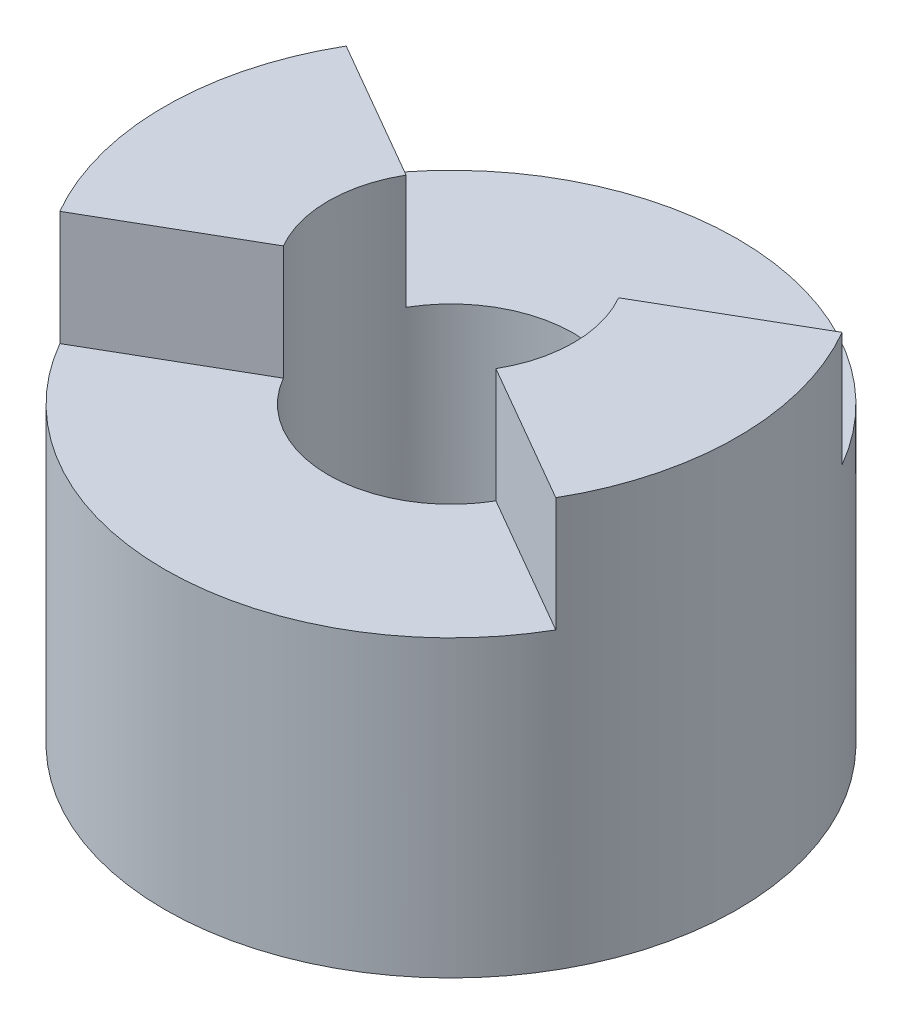
SolidWorks part; units mm, degrees
ref_plane "Front Plane" through (0, 0, 0) normal (0, 0, 1) x (1, 0, 0)
ref_plane "Top Plane" through (0, 0, 0) normal (0, 1, 0) x (1, 0, 0)
ref_plane "Right Plane" through (0, 0, 0) normal (1, 0, 0) x (0, 0, -1)
sketch "Sketch1" plane through (0, 0, 0) normal (0, 1, 0) x (1, 0, 0)
  circle A0 centre (0, 0) radius 35
  circle A1 centre (0, 0) radius 15
  dimension "D1" = 70
  dimension "D2" = 30
extrude "Boss-Extrude1" add sketch "Sketch1" along normal blind 50
sketch "Sketch2" plane through (0, 50, 0) normal (0, 1, 0) x (1, 0, 0)
  line L0 (0, 0) -> (45.0155, 0) construction
  line L1 (0, 0) -> (0, -60.2355) construction
  line L2 (12.9904, -7.5) -> (30.3109, -17.5)
  line L3 (-12.9904, -7.5) -> (-30.3109, -17.5)
  circle A0 centre (0, 0) radius 35 construction
  arc A1 (-30.3109, -17.5) -> (30.3109, -17.5) centre (0, 0) ccw
  circle A2 centre (0, 0) radius 15 construction
  arc A3 (-12.9904, -7.5) -> (12.9904, -7.5) centre (0, 0) ccw
  dimension "D1" = 120
extrude "Cut-Extrude1" cut sketch "Sketch2" against normal offset from surface (14 mm away) 36 up to face at (0, 0, 35)
ref_axis "Axis1" through (0, 50, 0) along (0, -1, 0)
mirror "Mirror1" about plane through (0, 0, 0) normal (0, 0, 1) of "Cut-Extrude1"
